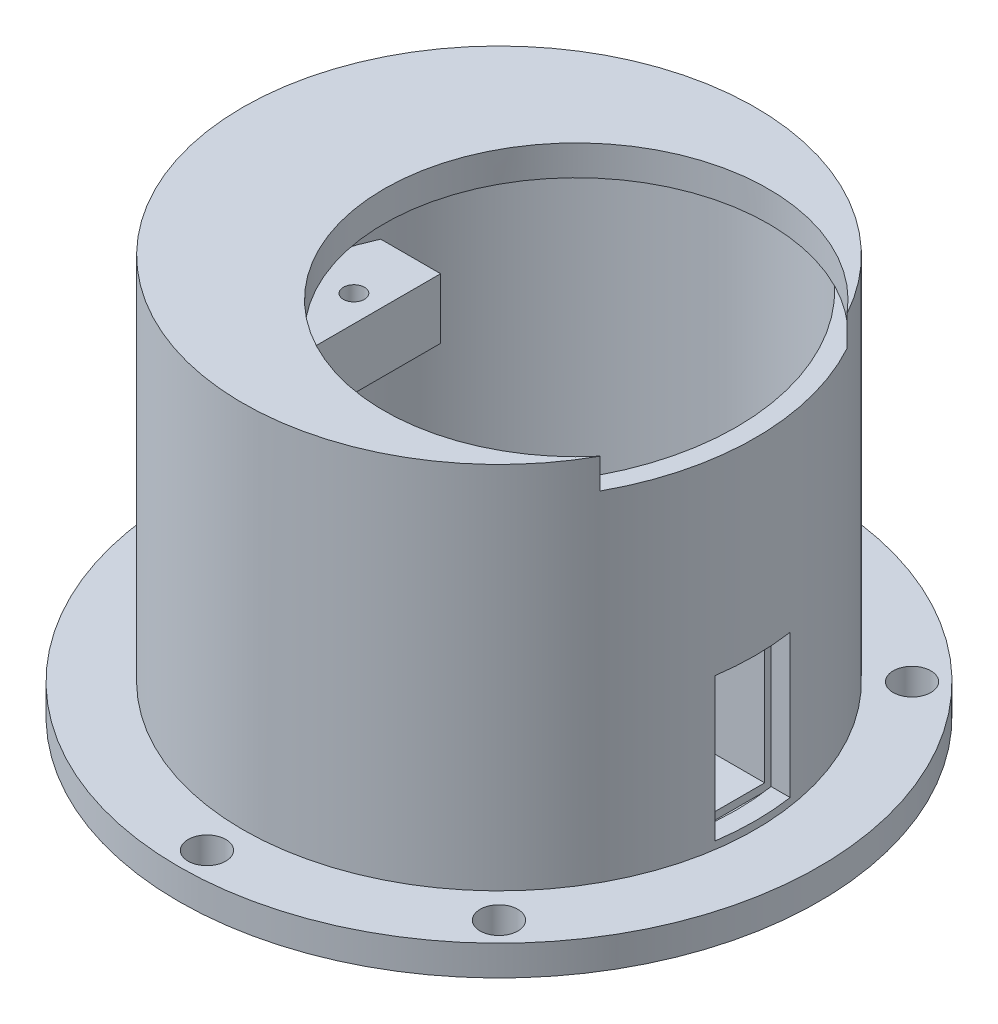
SolidWorks part; units mm, degrees
ref_plane "Front Plane" through (0, 0, 0) normal (0, 0, 1) x (1, 0, 0)
ref_plane "Top Plane" through (0, 0, 0) normal (0, 1, 0) x (1, 0, 0)
ref_plane "Right Plane" through (0, 0, 0) normal (1, 0, 0) x (0, 0, -1)
sketch "Sketch1" plane through (0, 0, 0) normal (0, 1, 0) x (1, 0, 0)
  circle A0 centre (0, 0) radius 30
  circle A1 centre (0, 0) radius 42.5
  dimension "D1" = 60
  dimension "D2" = 85
extrude "Boss-Extrude1" add sketch "Sketch1" along normal blind 4
sketch "Sketch2" plane through (0, 4, 0) normal (0, 1, 0) x (1, 0, 0)
  circle A3 centre (0, 0) radius 34
  circle A6 centre (0, 0) radius 31.5
  dimension "D1" = 63
extrude "Boss-Extrude2" add sketch "Sketch2" along normal blind 45
sketch "Sketch3" plane through (0, 0, 0) normal (0, 0, 1) x (1, 0, 0)
  line L0 (0, 0) -> (0, 49) construction
  line L1 (34, 49) -> (-34, 49) construction
  line L2 (-42.5, 0) -> (42.5, 0) construction
  line L3 (22.25, 0) -> (30.25, 0)
  line L4 (22.25, 0) -> (22.25, 34)
  line L5 (22.25, 34) -> (30.25, 34)
  line L6 (30.25, 0) -> (30.25, 34)
  line L8 (42.5, 4) -> (-42.5, 4) construction
  line L9 (-31.25, 34) -> (-20.75, 34)
  line L10 (-31.25, 34) -> (-31.25, 26)
  line L11 (-31.25, 26) -> (-20.75, 26)
  line L12 (-20.75, 34) -> (-20.75, 26)
  dimension "D1" = 8
  dimension "D2" = 22.25
  dimension "D3" = 30
  dimension "D4" = 22
  dimension "D5" = 8
  dimension "D6" = 20.75
  dimension "D7" = 10.5
extrude "Boss-Extrude3" add sketch "Sketch3" along normal mid plane 26
sketch "Sketch4" plane through (22.25, 0, 0) normal (-1, 0, 0) x (0, 0, 1)
  line L0 (0, 0) -> (0, 34) construction
  line L1 (13, 0) -> (-13, 0) construction
  line L2 (13, 34) -> (-13, 34) construction
  line L4 (-5, 5) -> (5, 5)
  line L5 (-5, 5) -> (-5, 24)
  line L6 (-5, 24) -> (5, 24)
  line L7 (5, 5) -> (5, 24)
  line L8 (-5, 5) -> (5, 24) construction
  line L9 (-5, 24) -> (5, 5) construction
  point P6 (0, 14.5)
  dimension "D1" = 5
  dimension "D2" = 10
  dimension "D3" = 10
extrude "Cut-Extrude1" cut sketch "Sketch4" against normal through all
sketch "Sketch6" plane through (0, 34, 0) normal (0, 1, 0) x (1, 0, 0)
  line L0 (-24.25, 13) -> (-24.25, -13) construction
  line L1 (-20.75, 13) -> (-28.6923, 13) construction
  line L2 (-20.75, -13) -> (-28.6923, -13) construction
  line L3 (-20.75, -13) -> (-20.75, 13) construction
  line L4 (-24.25, 0) -> (24.75, 0) construction
  line L6 (24.75, -13) -> (24.75, 13)
  line L7 (28.6923, 13) -> (22.25, 13) construction
  circle A0 centre (-24.25, -5) radius 1.4
  circle A1 centre (24.75, -5) radius 1.4
  circle A2 centre (24.75, 5) radius 1.4
  circle A3 centre (-24.25, 5) radius 1.4
  point P15 (24.75, 0)
  dimension "D3" = 2.8
  dimension "D1" = 3.5
  dimension "D2" = 49
  dimension "D4" = 5
extrude "Cut-Extrude3" cut sketch "Sketch6" against normal blind 7.2 contours A3 | A2 | A1 | A0
sketch "Sketch8" plane through (0, 4, 0) normal (0, 1, 0) x (1, 0, 0)
  line L0 (0, 0) -> (30.4574, -30.4574) construction
  line L1 (0, 0) -> (0, -46.2977) construction
  line L2 (0, 0) -> (30.4574, 30.4574) construction
  circle A0 centre (0, 0) radius 38.75 construction
  circle A1 centre (-38.75, 0) radius 2.5
  circle A2 centre (0, 38.75) radius 2.5
  circle A4 centre (0, -38.75) radius 2.5
  circle A5 centre (27.4004, -27.4004) radius 2.5
  circle A6 centre (27.4004, 27.4004) radius 2.5
  point P13 (0, 0)
  dimension "D1" = 77.5
  dimension "D2" = 5
  dimension "D4" = 5
  dimension "D5" = 225
  dimension "D6" = 5
  dimension "D3" = 45
extrude "Cut-Extrude4" cut sketch "Sketch8" against normal up to surface (4 mm away) up to face at (10.3843, 0, 0)
sketch "Sketch9" plane through (0, 49, 0) normal (0, 1, 0) x (1, 0, 0)
  circle A11 centre (10.25, 0) radius 25.5
  arc A12 (29.7957, 16.3773) -> (29.7957, -16.3773) centre (10.25, 0) ccw
  circle A14 centre (0, 0) radius 34
  arc A15 (29.7957, 16.3773) -> (29.7957, -16.3773) centre (0, 0) ccw
  dimension "D1" = 0.5
  dimension "D2" = 2.5
extrude "Boss-Extrude4" add sketch "Sketch9" along normal blind 4
